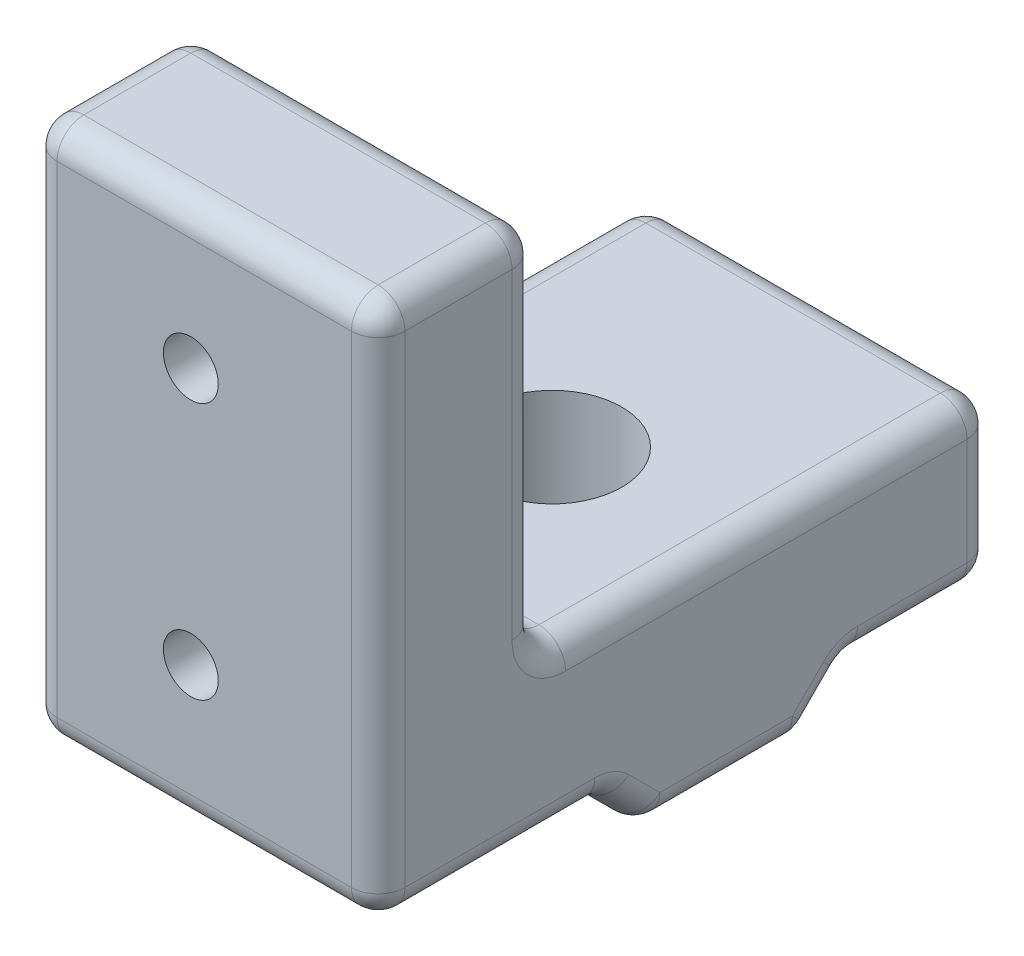
SolidWorks part; units mm, degrees
ref_plane "Front Plane" through (0, 0, 0) normal (0, 0, 1) x (1, 0, 0)
ref_plane "Top Plane" through (0, 0, 0) normal (0, 1, 0) x (1, 0, 0)
ref_plane "Right Plane" through (0, 0, 0) normal (1, 0, 0) x (0, 0, -1)
sketch "Sketch1" plane through (32.3643, 0, 0) normal (1, 0, 0) x (0, 0, -1)
  line L0 (-10.7659, 34.0751) -> (-4.9859, 34.0751)
  line L1 (-17.8759, 35.7651) -> (2.1241, 35.7651)
  line L2 (-17.8759, 35.7651) -> (-17.8759, 41.7651)
  line L3 (-17.8759, 41.7651) -> (2.1241, 41.7651)
  line L4 (2.1241, 35.7651) -> (2.1241, 41.7651)
  line L52 (-5.5365, 22.3651) -> (-2.3759, 19.2044)
  line L53 (-2.3759, 19.2044) -> (-2.3759, 17.5651)
  line L54 (-2.3759, 17.5651) -> (-4.9859, 17.5651)
  line L55 (-4.9859, 17.5651) -> (-4.9859, 17.4551)
  line L56 (-4.9859, 17.4551) -> (-3.5273, 15.9964)
  line L57 (-2.9686, 15.7651) -> (0.6241, 15.7651)
  line L58 (2.1241, 17.2651) -> (2.1241, 20.8578)
  line L59 (1.8927, 21.4164) -> (0.4341, 22.8751)
  line L60 (0.4341, 22.8751) -> (0.3241, 22.8751)
  line L61 (0.3241, 22.8751) -> (0.3241, 20.2651)
  line L62 (0.3241, 20.2651) -> (-1.3152, 20.2651)
  line L63 (-1.3152, 20.2651) -> (-4.4759, 23.4257)
  line L64 (-4.4759, 23.4257) -> (-4.4759, 28.1044)
  line L65 (-4.4759, 28.1044) -> (-1.3152, 31.2651)
  line L66 (-1.3152, 31.2651) -> (0.3241, 31.2651)
  line L67 (0.3241, 31.2651) -> (0.3241, 28.6551)
  line L68 (0.3241, 28.6551) -> (0.4341, 28.6551)
  line L69 (0.4341, 28.6551) -> (1.8927, 30.1137)
  line L70 (2.1241, 30.6723) -> (2.1241, 34.2651)
  line L71 (0.6241, 35.7651) -> (-2.9686, 35.7651)
  line L72 (-3.5273, 35.5337) -> (-4.9859, 34.0751)
  line L73 (-4.9859, 34.0751) -> (-4.9859, 33.9651)
  line L74 (-4.9859, 33.9651) -> (-2.3759, 33.9651)
  line L75 (-2.3759, 33.9651) -> (-2.3759, 32.3257)
  line L76 (-2.3759, 32.3257) -> (-5.5365, 29.1651)
  line L77 (-5.5365, 29.1651) -> (-10.2152, 29.1651)
  line L78 (-10.2152, 29.1651) -> (-13.3759, 32.3257)
  line L79 (-13.3759, 32.3257) -> (-13.3759, 33.9651)
  line L80 (-13.3759, 33.9651) -> (-10.7659, 33.9651)
  line L81 (-10.7659, 33.9651) -> (-10.7659, 34.0751)
  line L82 (-10.7659, 34.0751) -> (-12.2245, 35.5337)
  line L83 (-12.7831, 35.7651) -> (-16.3759, 35.7651)
  line L84 (-17.8759, 34.2651) -> (-17.8759, 30.6723)
  line L85 (-17.6445, 30.1137) -> (-16.1859, 28.6551)
  line L86 (-16.1859, 28.6551) -> (-16.0759, 28.6551)
  line L87 (-16.0759, 28.6551) -> (-16.0759, 31.2651)
  line L88 (-16.0759, 31.2651) -> (-14.4365, 31.2651)
  line L89 (-14.4365, 31.2651) -> (-11.2759, 28.1044)
  line L90 (-11.2759, 28.1044) -> (-11.2759, 23.4257)
  line L91 (-11.2759, 23.4257) -> (-14.4365, 20.2651)
  line L92 (-14.4365, 20.2651) -> (-16.0759, 20.2651)
  line L93 (-16.0759, 20.2651) -> (-16.0759, 22.8751)
  line L94 (-16.0759, 22.8751) -> (-16.1859, 22.8751)
  line L95 (-16.1859, 22.8751) -> (-17.6445, 21.4164)
  line L96 (-17.8759, 20.8578) -> (-17.8759, 17.2651)
  line L97 (-16.3759, 15.7651) -> (-12.7831, 15.7651)
  line L98 (-12.2245, 15.9964) -> (-10.7659, 17.4551)
  line L99 (-10.7659, 17.4551) -> (-10.7659, 17.5651)
  line L100 (-10.7659, 17.5651) -> (-13.3759, 17.5651)
  line L101 (-13.3759, 17.5651) -> (-13.3759, 19.2044)
  line L102 (-13.3759, 19.2044) -> (-10.2152, 22.3651)
  line L103 (-10.2152, 22.3651) -> (-5.5365, 22.3651)
  line L104 (-5.5365, 22.3651) -> (-2.3759, 19.2044)
  line L105 (-2.3759, 19.2044) -> (-2.3759, 17.5651)
  line L106 (-2.3759, 17.5651) -> (-4.9859, 17.5651)
  line L107 (-4.9859, 17.5651) -> (-4.9859, 17.4551)
  line L108 (-4.9859, 17.4551) -> (-3.5273, 15.9964)
  line L109 (-2.9686, 15.7651) -> (0.6241, 15.7651)
  line L110 (2.1241, 17.2651) -> (2.1241, 20.8578)
  line L111 (1.8927, 21.4164) -> (0.4341, 22.8751)
  line L112 (0.4341, 22.8751) -> (0.3241, 22.8751)
  line L113 (0.3241, 22.8751) -> (0.3241, 20.2651)
  line L114 (0.3241, 20.2651) -> (-1.3152, 20.2651)
  line L115 (-1.3152, 20.2651) -> (-4.4759, 23.4257)
  line L116 (-4.4759, 23.4257) -> (-4.4759, 28.1044)
  line L117 (-4.4759, 28.1044) -> (-1.3152, 31.2651)
  line L118 (-1.3152, 31.2651) -> (0.3241, 31.2651)
  line L119 (0.3241, 31.2651) -> (0.3241, 28.6551)
  line L120 (0.3241, 28.6551) -> (0.4341, 28.6551)
  line L121 (0.4341, 28.6551) -> (1.8927, 30.1137)
  line L122 (2.1241, 30.6723) -> (2.1241, 34.2651)
  line L123 (0.6241, 35.7651) -> (-2.9686, 35.7651)
  line L124 (-3.5273, 35.5337) -> (-4.9859, 34.0751)
  line L125 (-4.9859, 34.0751) -> (-4.9859, 33.9651)
  line L126 (-4.9859, 33.9651) -> (-2.3759, 33.9651)
  line L127 (-2.3759, 33.9651) -> (-2.3759, 32.3257)
  line L128 (-2.3759, 32.3257) -> (-5.5365, 29.1651)
  line L129 (-5.5365, 29.1651) -> (-10.2152, 29.1651)
  line L130 (-10.2152, 29.1651) -> (-13.3759, 32.3257)
  line L131 (-13.3759, 32.3257) -> (-13.3759, 33.9651)
  line L132 (-13.3759, 33.9651) -> (-10.7659, 33.9651)
  line L133 (-10.7659, 33.9651) -> (-10.7659, 34.0751)
  line L134 (-10.7659, 34.0751) -> (-12.2245, 35.5337)
  line L135 (-12.7831, 35.7651) -> (-16.3759, 35.7651)
  line L136 (-17.8759, 34.2651) -> (-17.8759, 30.6723)
  line L137 (-17.6445, 30.1137) -> (-16.1859, 28.6551)
  line L138 (-16.1859, 28.6551) -> (-16.0759, 28.6551)
  line L139 (-16.0759, 28.6551) -> (-16.0759, 31.2651)
  line L140 (-16.0759, 31.2651) -> (-14.4365, 31.2651)
  line L141 (-14.4365, 31.2651) -> (-11.2759, 28.1044)
  line L142 (-11.2759, 28.1044) -> (-11.2759, 23.4257)
  line L143 (-11.2759, 23.4257) -> (-14.4365, 20.2651)
  line L144 (-14.4365, 20.2651) -> (-16.0759, 20.2651)
  line L145 (-16.0759, 20.2651) -> (-16.0759, 22.8751)
  line L146 (-16.0759, 22.8751) -> (-16.1859, 22.8751)
  line L147 (-16.1859, 22.8751) -> (-17.6445, 21.4164)
  line L148 (-17.8759, 20.8578) -> (-17.8759, 17.2651)
  line L149 (-16.3759, 15.7651) -> (-12.7831, 15.7651)
  line L150 (-12.2245, 15.9964) -> (-10.7659, 17.4551)
  line L151 (-10.7659, 17.4551) -> (-10.7659, 17.5651)
  line L152 (-10.7659, 17.5651) -> (-13.3759, 17.5651)
  line L153 (-13.3759, 17.5651) -> (-13.3759, 19.2044)
  line L154 (-13.3759, 19.2044) -> (-10.2152, 22.3651)
  line L155 (-10.2152, 22.3651) -> (-5.5365, 22.3651)
  arc A12 (-3.5273, 15.9964) -> (-2.9686, 15.7651) centre (-2.9686, 16.5551) ccw
  arc A13 (0.6241, 15.7651) -> (2.1241, 17.2651) centre (0.6241, 17.2651) ccw
  arc A14 (2.1241, 20.8578) -> (1.8927, 21.4164) centre (1.3341, 20.8578) ccw
  arc A15 (1.8927, 30.1137) -> (2.1241, 30.6723) centre (1.3341, 30.6723) ccw
  arc A16 (2.1241, 34.2651) -> (0.6241, 35.7651) centre (0.6241, 34.2651) ccw
  arc A17 (-2.9686, 35.7651) -> (-3.5273, 35.5337) centre (-2.9686, 34.9751) ccw
  arc A18 (-12.2245, 35.5337) -> (-12.7831, 35.7651) centre (-12.7831, 34.9751) ccw
  arc A19 (-16.3759, 35.7651) -> (-17.8759, 34.2651) centre (-16.3759, 34.2651) ccw
  arc A20 (-17.8759, 30.6723) -> (-17.6445, 30.1137) centre (-17.0859, 30.6723) ccw
  arc A21 (-17.6445, 21.4164) -> (-17.8759, 20.8578) centre (-17.0859, 20.8578) ccw
  arc A22 (-17.8759, 17.2651) -> (-16.3759, 15.7651) centre (-16.3759, 17.2651) ccw
  arc A23 (-12.7831, 15.7651) -> (-12.2245, 15.9964) centre (-12.7831, 16.5551) ccw
  arc A24 (-3.5273, 15.9964) -> (-2.9686, 15.7651) centre (-2.9686, 16.5551) ccw
  arc A25 (0.6241, 15.7651) -> (2.1241, 17.2651) centre (0.6241, 17.2651) ccw
  arc A26 (2.1241, 20.8578) -> (1.8927, 21.4164) centre (1.3341, 20.8578) ccw
  arc A27 (1.8927, 30.1137) -> (2.1241, 30.6723) centre (1.3341, 30.6723) ccw
  arc A28 (2.1241, 34.2651) -> (0.6241, 35.7651) centre (0.6241, 34.2651) ccw
  arc A29 (-2.9686, 35.7651) -> (-3.5273, 35.5337) centre (-2.9686, 34.9751) ccw
  arc A30 (-12.2245, 35.5337) -> (-12.7831, 35.7651) centre (-12.7831, 34.9751) ccw
  arc A31 (-16.3759, 35.7651) -> (-17.8759, 34.2651) centre (-16.3759, 34.2651) ccw
  arc A32 (-17.8759, 30.6723) -> (-17.6445, 30.1137) centre (-17.0859, 30.6723) ccw
  arc A33 (-17.6445, 21.4164) -> (-17.8759, 20.8578) centre (-17.0859, 20.8578) ccw
  arc A34 (-17.8759, 17.2651) -> (-16.3759, 15.7651) centre (-16.3759, 17.2651) ccw
  arc A35 (-12.7831, 15.7651) -> (-12.2245, 15.9964) centre (-12.7831, 16.5551) ccw
  dimension "D2" = 6
  dimension "D1" = 0
extrude "Boss-Extrude1" add sketch "Sketch1" along normal blind 13 contours L1 L4 L3 L2 | A30 L134 L0 L124 A29 L1 region at (32.3643, 34.9853, 7.8759) region at (32.3643, 38.7651, 7.8759)
sketch "Sketch2" plane through (0, 34.0751, 0) normal (0, -1, 0) x (1, 0, 0)
  line L0 (45.3643, 4.9859) -> (32.3643, 10.7659) construction
  line L1 (32.3643, 10.7659) -> (32.3643, 4.9859) construction
  line L2 (32.3643, 4.9859) -> (45.3643, 10.7659) construction
  circle A0 centre (38.8643, 7.8759) radius 2.6
  dimension "D1" = 5.2
extrude "Cut-Extrude1" cut sketch "Sketch2" against normal up to next
sketch "Sketch3" plane through (0, 0, 17.8759) normal (0, 0, 1) x (1, 0, 0)
  line L1 (32.3643, 35.7651) -> (45.3643, 35.7651)
  line L2 (32.3643, 35.7651) -> (32.3643, 55.7651)
  line L3 (32.3643, 55.7651) -> (45.3643, 55.7651)
  line L4 (45.3643, 35.7651) -> (45.3643, 55.7651)
  line L6 (45.3643, 35.7651) -> (45.3643, 41.7651) construction
  dimension "D1" = 20
extrude "Boss-Extrude2" add sketch "Sketch3" along normal blind 3 and the other way blind 3
sketch "Sketch4" plane through (0, 0, 20.8759) normal (0, 0, 1) x (1, 0, 0)
  line L0 (32.3643, 55.7651) -> (32.3643, 35.7651) construction
  line L1 (32.3643, 35.7651) -> (45.3643, 35.7651) construction
  circle A0 centre (38.3643, 50.5651) radius 1.025
  circle A1 centre (38.3643, 40.9651) radius 1.025
  dimension "D1" = 6
  dimension "D5" = 2.05
  dimension "D6" = 2.05
  dimension "D2" = 6
  dimension "D3" = 9.6
  dimension "D4" = 5.2
extrude "Cut-Extrude2" cut sketch "Sketch4" against normal blind 5.9
fillet "Fillet1" radius 1 8 edges at (38.8643, 34.0751, 4.9859) (38.8643, 34.0751, 10.7659) (38.8643, 35.7651, -2.1241) (38.8643, 55.7651, 20.8759) (38.8643, 41.7651, -2.1241) (38.8643, 55.7651, 14.8759) (38.8643, 35.7651, 20.8759) (38.8643, 41.7651, 14.8759)
fillet "Fillet2" radius 1 40 edges at (32.3643, 42.058, 14.583) (32.3643, 48.7651, 14.8759) (32.3643, 55.4722, 15.1688) (32.3643, 55.7651, 17.8759) (32.3643, 55.4722, 20.583) (32.3643, 45.7651, 20.8759) (32.3643, 36.058, 20.583) (32.3643, 35.7651, 16.3295) (32.3643, 35.7049, 12.4808) (32.3643, 34.9508, 11.6416) (32.3643, 34.1512, 10.7343) (32.3643, 34.0751, 7.8759) (32.3643, 34.1512, 5.0174) (32.3643, 34.9508, 4.1101) (32.3643, 35.7049, 3.271) (32.3643, 35.7651, 0.9223) (32.3643, 36.058, -1.8312) (32.3643, 38.7651, -2.1241) (32.3643, 41.4722, -1.8312) (45.3643, 42.058, 14.583) (45.3643, 48.7651, 14.8759) (45.3643, 55.4722, 15.1688) (45.3643, 55.7651, 17.8759) (45.3643, 55.4722, 20.583) (45.3643, 45.7651, 20.8759) (45.3643, 36.058, 20.583) (45.3643, 35.7651, 16.3295) (45.3643, 35.7049, 12.4808) (45.3643, 34.9508, 11.6416) (45.3643, 34.1512, 10.7343) (45.3643, 34.0751, 7.8759) (45.3643, 34.1512, 5.0174) (45.3643, 34.9508, 4.1101) (45.3643, 35.7049, 3.271) (45.3643, 35.7651, 0.9223) (45.3643, 36.058, -1.8312) (45.3643, 38.7651, -2.1241) (45.3643, 41.4722, -1.8312) (32.3643, 41.7651, 6.3759) (45.3643, 41.7651, 6.3759)
